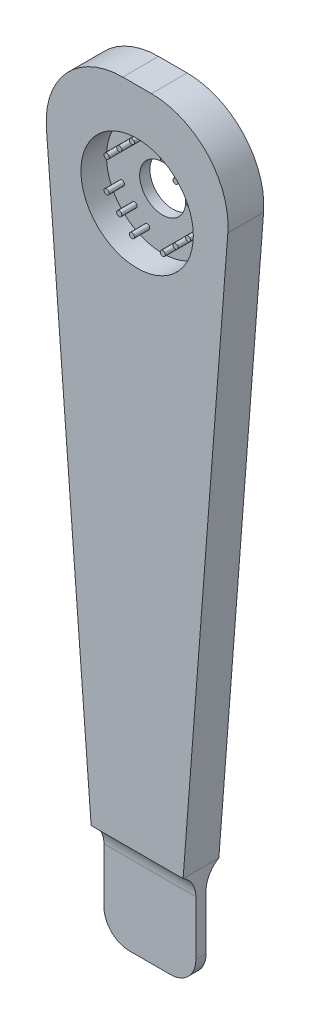
SolidWorks part; units mm, degrees
ref_plane "Plan de face" through (0, 0, 0) normal (0, 0, 1) x (1, 0, 0)
ref_plane "Plan de dessus" through (0, 0, 0) normal (0, 1, 0) x (1, 0, 0)
ref_plane "Plan de droite" through (0, 0, 0) normal (1, 0, 0) x (0, 0, -1)
sketch "Esquisse1" plane through (0, 0, 0) normal (0, 0, 1) x (1, 0, 0)
  line L2 (0, 150) -> (18, 150)
  line L4 (0, 150) -> (-10, 150)
  line L5 (-10, 150) -> (0, 20)
  line L6 (0, 20) -> (18, 20)
  line L7 (18, 20) -> (28, 150)
  line L8 (28, 150) -> (18, 150)
  line L9 (0, 150) -> (18, 150)
  line L10 (0, 20) -> (0, 0)
  line L11 (18, 0) -> (18, 20)
  line L12 (0, 20) -> (0, 0)
  line L13 (18, 0) -> (0, 0)
  circle A0 centre (9, 130) radius 4.5
  point P9 (38, 150)
  dimension "D3" = 9
  dimension "D1" = 18
  dimension "D2" = 150
  dimension "D4" = 130
  dimension "D5" = 20
  dimension "D6" = 10
  dimension "D7" = 10
  dimension "D8" = 20
  dimension "D9" = 18
  dimension "D10" = 19
extrude "Boss.-Extru.1" add sketch "Esquisse1" along normal blind 7 contours L7 L8 L2 L4 L5 L6 A0 | L13 L11 L6 L10 region at (9, 92.0753, 0) region at (9, 10, 0)
sketch "Esquisse2" plane through (0, 0, 7) normal (0, 0, 1) x (1, 0, 0)
  circle A0 centre (9, 130) radius 11
  dimension "D1" = 22
extrude "Enlèv. mat.-Extru.1" cut sketch "Esquisse2" against normal blind 5
sketch "Esquisse3" plane through (0, 0, 2) normal (0, 0, 1) x (1, 0, 0)
  line L0 (9, 141) -> (9, 119) construction
  line L1 (9, 119) -> (-2, 130) construction
  line L2 (-2, 130) -> (9, 141) construction
  line L3 (9, 141) -> (20, 130) construction
  line L4 (20, 130) -> (9, 119) construction
  line L5 (-2, 130) -> (20, 130) construction
  circle A0 centre (9, 130) radius 11 construction
  circle A1 centre (9, 130) radius 11 construction
  circle A2 centre (3.5, 135.5) radius 0.5
  circle A3 centre (5.9749, 137.9749) radius 0.5
  circle A4 centre (1.0251, 133.0251) radius 0.5
  circle A5 centre (1.0251, 126.9749) radius 0.5
  circle A6 centre (3.5, 124.5) radius 0.5
  circle A7 centre (5.9749, 122.0251) radius 0.5
  circle A8 centre (12.0251, 122.0251) radius 0.5
  circle A9 centre (14.5, 124.5) radius 0.5
  circle A10 centre (16.9749, 126.9749) radius 0.5
  circle A11 centre (16.9749, 133.0251) radius 0.5
  circle A12 centre (14.5, 135.5) radius 0.5
  circle A13 centre (12.0251, 137.9749) radius 0.5
  point P33 (0, 0)
  point P34 (14.9068, 135.0932)
  point P35 (3.5, 135.5)
  point P36 (3.5, 135.5)
  point P37 (3.5, 124.5)
  point P38 (0, 0)
  point P39 (17.674, 127.7748)
  point P40 (17.674, 132.0305)
  point P41 (5.9906, 137.8535)
  point P42 (11.944, 138.1689)
  point P43 (11.8875, 122.0094)
  point P44 (0.0305, 127.674)
  point P45 (0.1782, 132.1782)
  point P46 (17.8218, 127.8218)
  point P47 (0, 0)
  dimension "D9" = 1
  dimension "D1" = 7
  dimension "D2" = 3.5
  dimension "D3" = 3.5
  dimension "D4" = 7
  dimension "D5" = 3.5
  dimension "D6" = 7
  dimension "D7" = 3.5
  dimension "D8" = 7
extrude "Boss.-Extru.2" add sketch "Esquisse3" along normal blind 3
sketch "Esquisse4" plane through (0, 0, 7) normal (0, 0, 1) x (1, 0, 0)
  line L0 (0, 0) -> (18, 0)
  line L1 (0, 0) -> (0, 20)
  line L2 (18, 0) -> (18, 20)
  line L3 (0, 20) -> (18, 20)
  point P0 (18, 20)
extrude "Enlèv. mat.-Extru.2" cut sketch "Esquisse4" against normal blind 2.5
sketch "Esquisse5" plane through (0, 0, 0) normal (0, 0, -1) x (-1, 0, 0)
  line L0 (0, 0) -> (0, 20)
  line L1 (0, 0) -> (-18, 0)
  line L2 (0, 20) -> (-18, 20)
  line L3 (-18, 0) -> (-18, 20)
  point P0 (-18, 0)
extrude "Enlèv. mat.-Extru.3" cut sketch "Esquisse5" against normal blind 2.5
fillet "Congé1" radius 5 4 edges at (9, 20, 4.5) (9, 20, 2.5) (0, 0, 3.5) (18, 0, 3.5)
fillet "Congé2" radius 15 2 edges at (28, 150, 3.5) (-10, 150, 3.5)
equation "\"cm\"=5"
